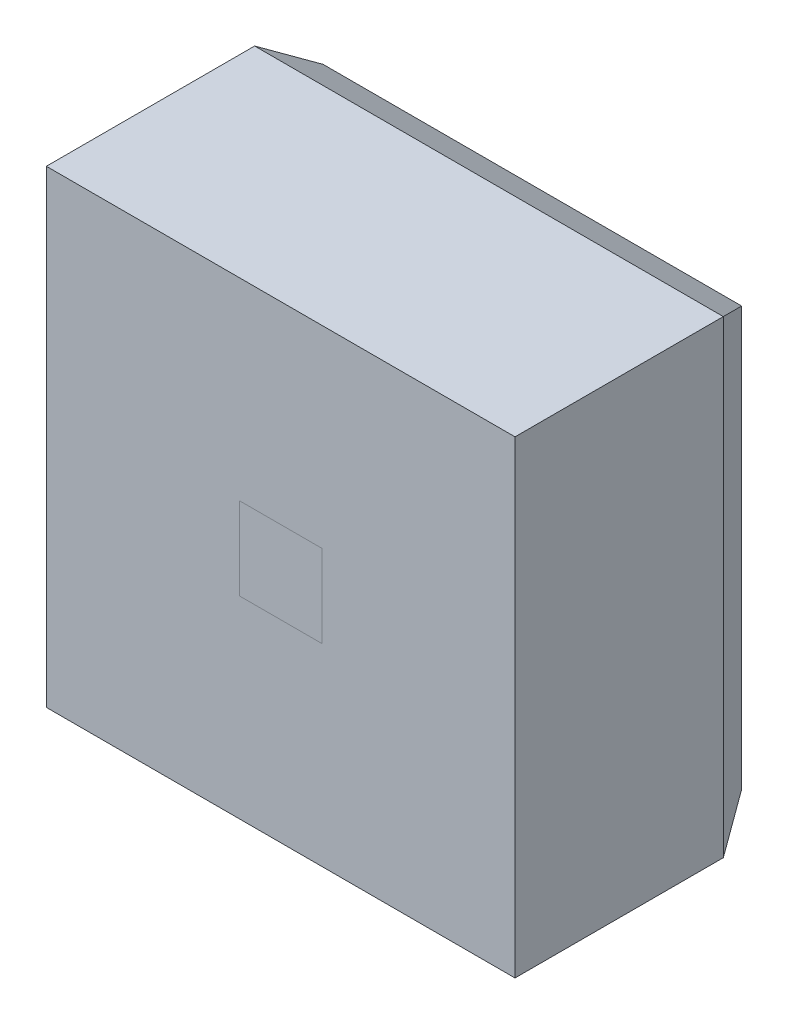
SolidWorks part; units mm, degrees
ref_plane "Front Plane" through (0, 0, 0) normal (0, 0, 1) x (1, 0, 0)
ref_plane "Top Plane" through (0, 0, 0) normal (0, 1, 0) x (1, 0, 0)
ref_plane "Right Plane" through (0, 0, 0) normal (1, 0, 0) x (0, 0, -1)
ref_axis "Axis1" through (0, 0, 0) along (0, 1, 0)
sketch "Sketch1" plane through (0, 0, 0) normal (0, 0, 1) x (1, 0, 0)
  line L0 (0, 0.54) -> (0, -0.54) construction
  line L1 (-0.54, 0.54) -> (0.54, 0.54)
  line L2 (-0.54, 0.54) -> (-0.54, -0.54)
  line L3 (-0.54, -0.54) -> (0.54, -0.54)
  line L4 (0.54, 0.54) -> (0.54, -0.54)
  line L5 (-0.54, 0) -> (0.54, 0) construction
  dimension "D1" = 1.08
sketch "Sketch2" plane through (0, 0, 0) normal (0, 0, 1) x (1, 0, 0)
  line L0 (-0.54, 0.54) -> (0.54, 0.54) construction
  line L1 (0.54, 0.54) -> (0.54, -0.54) construction
  line L2 (-0.54, -0.54) -> (0.54, -0.54) construction
  line L3 (-0.54, 0.54) -> (-0.54, -0.54) construction
  line L4 (-0.54, 0.54) -> (0.54, 0.54)
  line L5 (0.54, 0.54) -> (0.54, -0.54)
  line L6 (-0.54, -0.54) -> (0.54, -0.54)
  line L7 (-0.54, 0.54) -> (-0.54, -0.54)
extrude "Boss-Extrude1" add sketch "Sketch2" along normal blind 0.68
other "Move Face1" flip direction yes face at (0, 0, 0) offset 0.1 parameters "D1"=0.1
chamfer "Chamfer1" distance 0.1 angle 30 4 edges at (0, -0.54, 0.1) (0.54, 0, 0.1) (0, 0.54, 0.1) (-0.54, 0, 0.1) first distance on face at (0, -0.54, 0.39) first distance on face at (0.54, 0, 0.39) first distance on face at (0, 0.54, 0.39) first distance on face at (-0.54, 0, 0.39)
sketch "Sketch3" plane through (0, 0, 0) normal (0, 0, 1) x (1, 0, 0)
  line L1 (0.25, -0.25) -> (-0.25, -0.25) construction
  line L2 (0.25, -0.25) -> (0.25, 0.25) construction
  line L3 (0.25, 0.25) -> (-0.25, 0.25) construction
  line L4 (-0.25, -0.25) -> (-0.25, 0.25) construction
  line L5 (0.25, -0.25) -> (-0.25, 0.25) construction
  line L6 (0.25, 0.25) -> (-0.25, -0.25) construction
  circle A0 centre (-0.25, 0.25) radius 0.125
  circle A2 centre (0.25, -0.25) radius 0.125
  circle A3 centre (0.25, 0.25) radius 0.125
  circle A4 centre (-0.25, -0.25) radius 0.125
  dimension "D1" = 0.25
  dimension "D2" = 0.25
extrude "Boss-Extrude2" add sketch "Sketch3" along normal blind 0.1
fillet "Fillet1" radius 0.125 4 edges at (0.375, 0.25, 0) (0.125, -0.25, 0) (-0.375, -0.25, 0) (-0.125, 0.25, 0)
sketch "Sketch4" plane through (0, 0, 0) normal (0, 0, 1) x (1, 0, 0)
  line L1 (-0.095, -0.095) -> (0.095, -0.095)
  line L2 (-0.095, -0.095) -> (-0.095, 0.095)
  line L3 (-0.095, 0.095) -> (0.095, 0.095)
  line L4 (0.095, -0.095) -> (0.095, 0.095)
  line L5 (-0.095, -0.095) -> (0.095, 0.095) construction
  line L6 (-0.095, 0.095) -> (0.095, -0.095) construction
  dimension "D1" = 0.19
split line "Split Line1"
